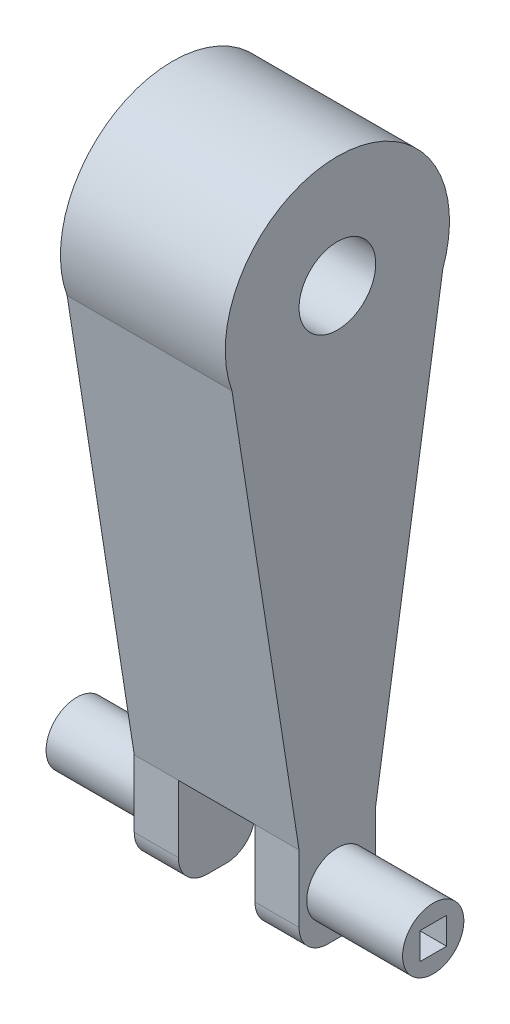
SolidWorks part; units mm, degrees
material "Commercialement pur CP-Ti UNS R50400 (SS)"
ref_plane "Plan de face" through (0, 0, 0) normal (0, 0, 1) x (1, 0, 0)
ref_plane "Plan de dessus" through (0, 0, 0) normal (0, 1, 0) x (1, 0, 0)
ref_plane "Plan de droite" through (0, 0, 0) normal (1, 0, 0) x (0, 0, -1)
sketch "Esquisse1" plane through (0, 0, 0) normal (1, 0, 0) x (0, 0, -1)
  line L0 (-292.5, 0) -> (292.5, 0) construction
  line L1 (-275, -99.6557) -> (275, -99.6557)
  line L2 (-80.5556, -1349.6557) -> (80.5556, -1349.6557)
  line L3 (80.5556, -1349.6557) -> (275, -99.6557)
  line L4 (-275, -99.6557) -> (-80.5556, -1349.6557)
  line L5 (0, -99.6557) -> (0, -1349.6557) construction
  line L7 (25, -1474.6557) -> (-25, -1474.6557)
  line L8 (100, -1399.6557) -> (100, -1224.6557)
  line L9 (100, -1224.6557) -> (-100, -1224.6557)
  line L10 (-100, -1399.6557) -> (-100, -1224.6557)
  line L11 (100, -1474.6557) -> (-100, -1224.6557) construction
  line L12 (100, -1224.6557) -> (-100, -1474.6557) construction
  circle A0 centre (0, 0) radius 100
  circle A1 centre (0, 0) radius 292.5
  circle A2 centre (0, -1349.6557) radius 80
  arc A3 (25, -1474.6557) -> (100, -1399.6557) centre (25, -1399.6557) ccw
  arc A4 (-25, -1474.6557) -> (-100, -1399.6557) centre (-25, -1399.6557) cw
  dimension "D1" = 200
  dimension "D2" = 585
  dimension "D7" = 160
  dimension "D8" = 75
  dimension "D3" = 550
  dimension "D4" = 1250
  dimension "D5" = 250
  dimension "D6" = 200
extrude "Boss.-Extru.1" add sketch "Esquisse1" along normal blind 430 contours L1 A1 A0 | L1 A1 A0 | A1 L4 L9 L3 | A2 L2 L3 L9 L4 | A4 L7 A3 L8 L3 L2 A2 L4 L10 region at (0, 281.1551, 49.3722) region at (0, -663.2208, 0) region at (0, -179.5011, 0) region at (0, -1260.1812, 0) region at (0, -1287.6478, 93.4413)
sketch "Esquisse2" plane through (0, 0, 100) normal (0, 0, 1) x (1, 0, 0)
  line L0 (430, -1224.6557) -> (0, -1224.6557) construction
  line L1 (115, -1224.6557) -> (315, -1224.6557)
  line L2 (115, -1224.6557) -> (115, -1474.6557)
  line L3 (115, -1474.6557) -> (315, -1474.6557)
  line L4 (315, -1224.6557) -> (315, -1474.6557)
  line L5 (430, -1474.6557) -> (0, -1474.6557) construction
  dimension "D1" = 200
  dimension "D2" = 115
  dimension "D3" = 115
  dimension "D4" = 250
extrude "Boss.-Extru.2" add sketch "Esquisse1<3>" against normal blind 250 separate body contours L2 A2 | L2 A2 region at (0, -1315.7026, 0) region at (0, -1383.6087, 0)
sketch "Esquisse1<3>" plane through (0, 0, 0) normal (1, 0, 0) x (0, 0, -1) same geometry as "Esquisse1"
extrude "Boss.-Extru.3" add sketch "Esquisse1<5>" along normal blind 680 contours L2 A2 | L2 A2 region at (0, -1315.7026, 0) region at (0, -1383.6087, 0)
sketch "Esquisse1<5>" plane through (0, 0, 0) normal (1, 0, 0) x (0, 0, -1) same geometry as "Esquisse1"
extrude "Enlèv. mat.-Extru.2" cut sketch "Esquisse2" against normal blind 680
sketch "Esquisse3" plane through (-250, 0, 0) normal (-1, 0, 0) x (0, 0, 1)
  line L1 (-35, -1384.6557) -> (35, -1384.6557)
  line L2 (-35, -1384.6557) -> (-35, -1314.6557)
  line L3 (-35, -1314.6557) -> (35, -1314.6557)
  line L4 (35, -1384.6557) -> (35, -1314.6557)
  line L5 (-35, -1384.6557) -> (35, -1314.6557) construction
  line L6 (-35, -1314.6557) -> (35, -1384.6557) construction
  point P0 (0, -1349.6557)
  dimension "D1" = 70
  dimension "D2" = 70
extrude "Enlèv. mat.-Extru.3" cut sketch "Esquisse3" against normal blind 100
sketch "Esquisse4" plane through (680, 0, 0) normal (1, 0, 0) x (0, 0, -1)
  line L1 (-35, -1384.6557) -> (35, -1384.6557)
  line L2 (-35, -1384.6557) -> (-35, -1314.6557)
  line L3 (-35, -1314.6557) -> (35, -1314.6557)
  line L4 (35, -1384.6557) -> (35, -1314.6557)
  line L5 (-35, -1384.6557) -> (35, -1314.6557) construction
  line L6 (-35, -1314.6557) -> (35, -1384.6557) construction
  point P0 (0, -1349.6557)
  dimension "D1" = 70
  dimension "D2" = 70
extrude "Enlèv. mat.-Extru.4" cut sketch "Esquisse4" against normal blind 100
